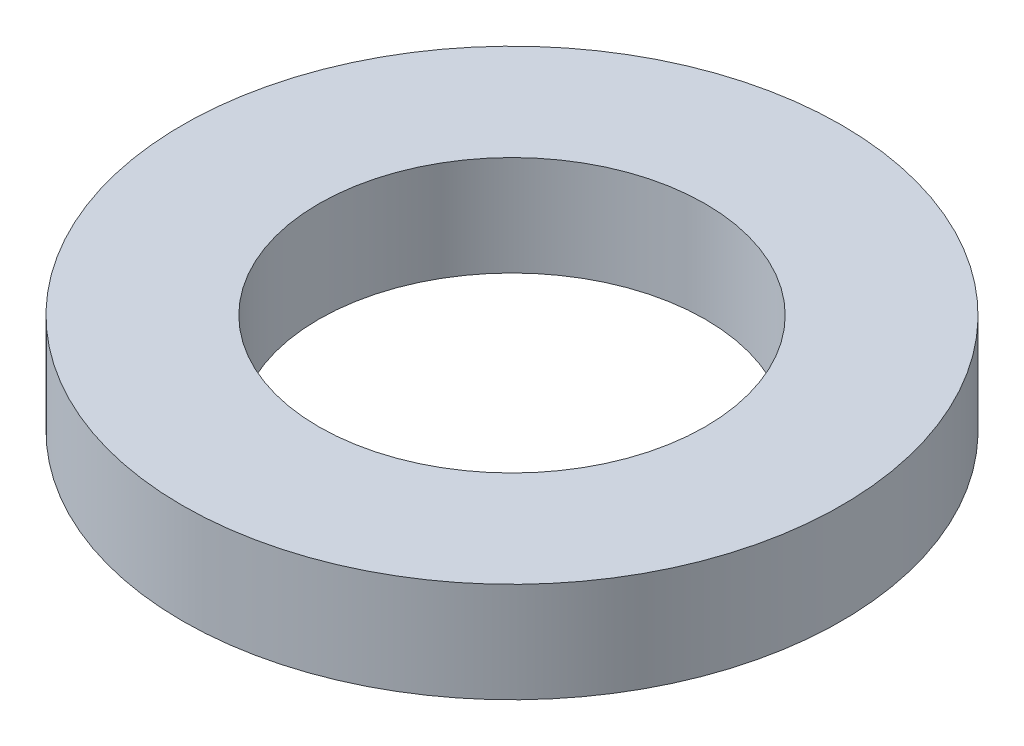
SolidWorks part; units mm, degrees
ref_plane "Front Plane" through (0, 0, 0) normal (0, 0, 1) x (1, 0, 0)
ref_plane "Top Plane" through (0, 0, 0) normal (0, 1, 0) x (1, 0, 0)
ref_plane "Right Plane" through (0, 0, 0) normal (1, 0, 0) x (0, 0, -1)
sketch "Sketch1" plane through (0, 0, 0) normal (0, 1, 0) x (1, 0, 0)
  circle A0 centre (0, 0) radius 72.5
  dimension "FLANGE_OD" = 145
extrude "Boss-Extrude1" add sketch "Sketch1" along normal blind 22
sketch "Sketch2" plane through (0, 0, 0) normal (0, 1, 0) x (1, 0, 0)
  circle A0 centre (0, 0) radius 42.5
  dimension "BORE_D" = 85
extrude "Cut-Extrude1" cut sketch "Sketch2" along normal through all
sketch "Sketch3" plane through (0, 22, 0) normal (0, 1, 0) x (1, 0, 0)
  circle A0 centre (0, 0) radius 23.8731 construction
  circle A1 centre (-23.8731, 0) radius 2.0804
  dimension "BOLT_D" = 4.1608
  dimension "BOLT_PCD" = 47.7461
extrude "Cut-Extrude2" cut sketch "Sketch3" against normal blind 15.4943 rebuild error yes
pattern_circular "CirPattern1" count 4 over 360 rebuild error yes
